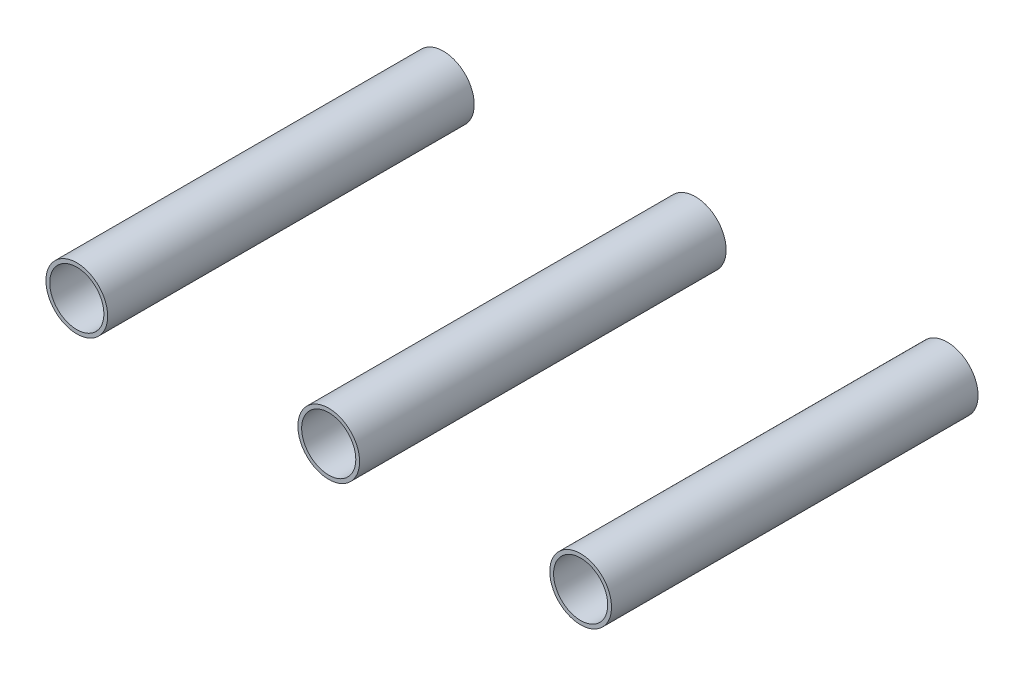
SolidWorks part; units mm, degrees
ref_plane "Front Plane" through (0, 0, 0) normal (0, 0, 1) x (1, 0, 0)
ref_plane "Top Plane" through (0, 0, 0) normal (0, 1, 0) x (1, 0, 0)
ref_plane "Right Plane" through (0, 0, 0) normal (1, 0, 0) x (0, 0, -1)
sketch "Sketch1" plane through (0, 0, 0) normal (0, 0, 1) x (1, 0, 0)
  line L0 (-29.2337, 0) -> (25.6022, 0) construction
  line L1 (0, 20.4903) -> (0, -22.7685) construction
  circle A0 centre (0, 0) radius 1.225
  circle A1 centre (-10, 0) radius 1.225
  circle A2 centre (10, 0) radius 1.225
  dimension "D1" = 2.45
  dimension "D2" = 10
extrude "Boss-Extrude1" add sketch "Sketch1" along normal blind 14.55
sketch "Sketch2" plane through (0, 0, 14.55) normal (0, 0, 1) x (1, 0, 0)
  circle A0 centre (-10, 0) radius 1.075
  circle A1 centre (0, 0) radius 1.075
  circle A2 centre (10, 0) radius 1.075
  circle A3 centre (-10, 0) radius 1.225 construction
  dimension "D1" = 0.15
extrude "Cut-Extrude1" cut sketch "Sketch2" against normal offset from surface (11.55 mm away) 3 up to face at (-8.775, 0, 0)
sketch "Sketch3" plane through (0, 0, 0) normal (0, 0, -1) x (-1, 0, 0)
  circle A0 centre (-10, 0) radius 1.075
  circle A1 centre (0, 0) radius 1.075
  circle A2 centre (10, 0) radius 1.075
  circle A3 centre (-10, 0) radius 1.075 construction
extrude "Cut-Extrude2" cut sketch "Sketch3" against normal offset from surface (2.85 mm away) 0.15 up to face at (-8.925, 0, 3)
